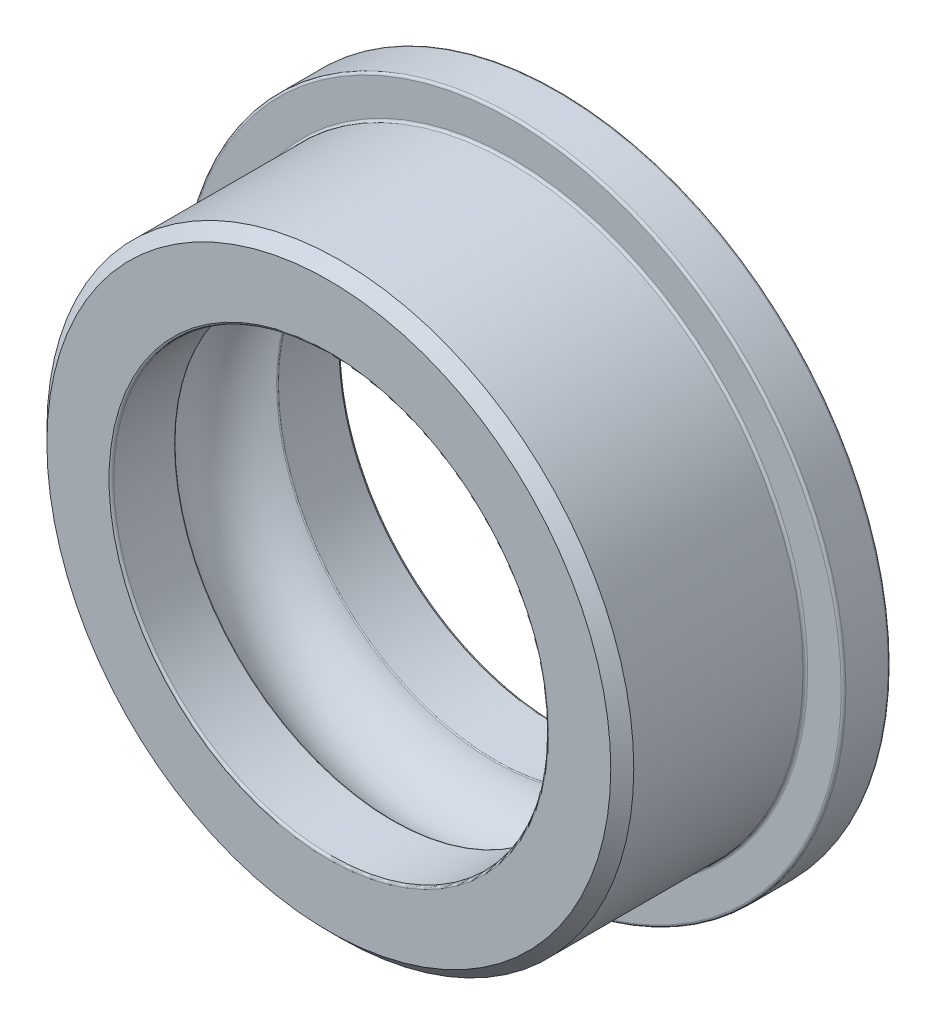
SolidWorks part; units mm, degrees
material "Stainless Steel (ferritic)"
ref_plane "Front Plane" through (0, 0, 0) normal (0, 0, 1) x (1, 0, 0)
ref_plane "Top Plane" through (0, 0, 0) normal (0, 1, 0) x (1, 0, 0)
ref_plane "Right Plane" through (0, 0, 0) normal (1, 0, 0) x (0, 0, -1)
ref_axis "Central Axis" through (0, 0, -2.7381) along (0, 0, 1)
sketch "Outer Bearing Race Profile" plane through (0, 0, 0) normal (1, 0, 0) x (0, 0, -1)
  line L0 (-2.4892, 0) -> (2.4892, 0) construction
  line L1 (0, 6.35) -> (0, -6.35) construction
  line L2 (1.4224, 6.35) -> (-2.2403, 6.35)
  line L3 (-2.2403, 6.35) -> (-2.4892, 6.1011)
  line L4 (-2.4892, 6.1011) -> (-2.4892, 4.7558)
  line L5 (-2.4384, 4.705) -> (-1.1249, 4.705)
  line L6 (2.4384, 4.705) -> (1.1249, 4.705)
  line L7 (2.4892, 7.1247) -> (2.4892, 4.7558)
  line L9 (0, 6.35) -> (0, 4.3656) construction
  line L10 (0, 4.3656) -> (0, 2.3813) construction
  line L11 (1.4732, 6.4008) -> (1.4732, 7.1247)
  line L12 (1.524, 7.1755) -> (2.4384, 7.1755)
  arc A0 (-1.1008, 4.7226) -> (1.1008, 4.7226) centre (0, 4.3656) cw
  arc A1 (2.4892, 4.7558) -> (2.4384, 4.705) centre (2.4384, 4.7558) cw
  arc A2 (-2.4892, 4.7558) -> (-2.4384, 4.705) centre (-2.4384, 4.7558) ccw
  arc A3 (1.4224, 6.35) -> (1.4732, 6.4008) centre (1.4224, 6.4008) ccw
  arc A4 (2.4892, 7.1247) -> (2.4384, 7.1755) centre (2.4384, 7.1247) ccw
  arc A5 (1.524, 7.1755) -> (1.4732, 7.1247) centre (1.524, 7.1247) ccw
  arc A6 (1.1249, 4.705) -> (1.1008, 4.7226) centre (1.1249, 4.7304) cw
  arc A7 (-1.1249, 4.705) -> (-1.1008, 4.7226) centre (-1.1249, 4.7304) ccw
  point P14 (0, 2.3813)
  point P18 (2.4892, 4.705)
  point P22 (-2.4892, 4.705)
  point P30 (2.4892, 7.1755)
  point P33 (1.4732, 7.1755)
  point P36 (1.1063, 4.705)
  point P39 (-1.1063, 4.705)
  dimension "D5" = 0.0508
  dimension "D8" = 0.0508
  dimension "D9" = 0.0254
  dimension "Width" = 4.9784
  dimension "OD" = 12.7
  dimension "D1" = 45
  dimension "D2" = 0.2489
  dimension "Shaft Dia" = 4.7625
  dimension "D3" = 2.2126
  dimension "D4" = 0.3394
  dimension "D6" = 14.351
  dimension "D7" = 1.016
  dimension "D10" = 5.5228
revolve "Outer Bearing Race" add sketch "Outer Bearing Race Profile" angle 360 about L0
sketch "Inner Race Bearing Gear Profile" plane through (0, 0, 0) normal (0, 0, 1) x (1, 0, 0)
  circle A0 centre (0, 0) radius 5.5228
  circle A1 centre (0, 0) radius 5.5228
curve "Inner Race Bearing Gear Curve"
equation "\"D2@Outer Bearing Race Profile\"= \"Width@Outer Bearing Race Profile\" * .05"
equation "\"D3@Outer Bearing Race Profile\" = \"Width@Outer Bearing Race Profile\" / 2.25"
equation "\"D4@Outer Bearing Race Profile\" =  (  (  ( \"OD@Outer Bearing Race Profile\" - \"Width@Outer Bearing Race Profile\" )  / 2 )  / 3.25 )  / 3.5"
